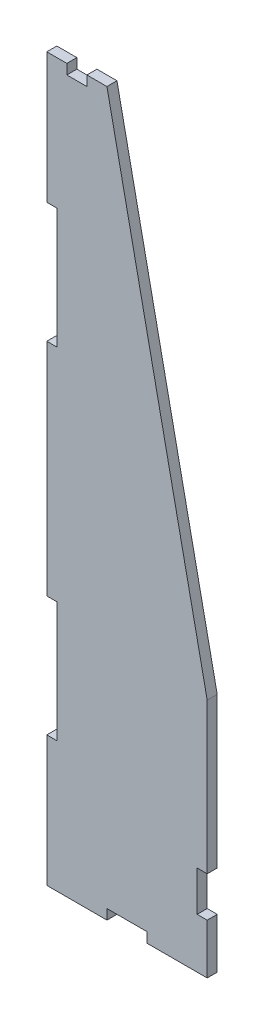
SolidWorks part; units mm, degrees
ref_plane "Front Plane" through (0, 0, 0) normal (0, 0, 1) x (1, 0, 0)
ref_plane "Top Plane" through (0, 0, 0) normal (0, 1, 0) x (1, 0, 0)
ref_plane "Right Plane" through (0, 0, 0) normal (1, 0, 0) x (0, 0, -1)
sketch "Sketch1" plane through (0, 0, 0) normal (0, 0, 1) x (1, 0, 0)
  line L0 (359.3199, 642.8699) -> (422.8199, 338.0699)
  line L1 (321.2199, 642.8699) -> (359.3199, 642.8699)
  line L2 (321.2199, 642.8699) -> (321.2199, 185.6699)
  line L3 (321.2199, 185.6699) -> (422.8199, 185.6699)
  line L4 (422.8199, 338.0699) -> (422.8199, 185.6699)
  dimension "D1" = 101.6
  dimension "D2" = 457.2
  dimension "D3" = 38.1
extrude "Boss-Extrude3" add sketch "Sketch1" along normal blind 6.35
sketch "Sketch2" plane through (0, 0, 6.35) normal (0, 0, 1) x (1, 0, 0)
  line L0 (327.5699, 642.8699) -> (327.5699, 185.6699) construction
  line L1 (359.3199, 642.8699) -> (321.2199, 642.8699) construction
  line L2 (321.2199, 185.6699) -> (422.8199, 185.6699) construction
  line L3 (321.2199, 192.0199) -> (422.8199, 192.0199) construction
  line L4 (321.2199, 642.8699) -> (321.2199, 185.6699) construction
  line L5 (422.8199, 185.6699) -> (422.8199, 338.0699) construction
  line L6 (321.2199, 636.5199) -> (360.6428, 636.5199) construction
  line L7 (416.4699, 185.6699) -> (416.4699, 368.5499) construction
  line L8 (422.8199, 338.0699) -> (359.3199, 642.8699) construction
  line L10 (346.6199, 642.8699) -> (333.9199, 642.8699)
  line L11 (346.6199, 642.8699) -> (346.6199, 636.5199)
  line L12 (346.6199, 636.5199) -> (333.9199, 636.5199)
  line L13 (333.9199, 642.8699) -> (333.9199, 636.5199)
  line L14 (321.2199, 560.3199) -> (327.5699, 560.3199)
  line L15 (321.2199, 560.3199) -> (321.2199, 484.1199)
  line L16 (321.2199, 484.1199) -> (327.5699, 484.1199)
  line L17 (327.5699, 560.3199) -> (327.5699, 484.1199)
  line L18 (321.2199, 344.4199) -> (327.5699, 344.4199)
  line L19 (321.2199, 344.4199) -> (321.2199, 268.2199)
  line L20 (321.2199, 268.2199) -> (327.5699, 268.2199)
  line L21 (327.5699, 344.4199) -> (327.5699, 268.2199)
  line L22 (359.3199, 192.0199) -> (384.7199, 192.0199)
  line L23 (359.3199, 192.0199) -> (359.3199, 185.6699)
  line L24 (359.3199, 185.6699) -> (384.7199, 185.6699)
  line L25 (384.7199, 192.0199) -> (384.7199, 185.6699)
  line L30 (416.4699, 242.8199) -> (422.8199, 242.8199)
  line L31 (416.4699, 242.8199) -> (416.4699, 217.4199)
  line L32 (416.4699, 217.4199) -> (422.8199, 217.4199)
  line L33 (422.8199, 242.8199) -> (422.8199, 217.4199)
  point P38 (419.6449, 217.4199)
  dimension "D1" = 6.35
  dimension "D2" = 6.35
  dimension "D3" = 6.35
  dimension "D4" = 6.35
  dimension "D6" = 12.7
  dimension "D8" = 82.55
  dimension "D9" = 82.55
  dimension "D10" = 25.4
  dimension "D14" = 31.75
  dimension "D7" = 25.4
  dimension "D13" = 38.1
  dimension "D5" = 12.7
  dimension "D11" = 76.2
extrude "Cut-Extrude1" cut sketch "Sketch2" against normal through all
equation "\"width\"= 3.5in"
equation "\"Height\"= 18in"
equation "\"D3@Sketch1\"=1.5"
equation "\"D4@Sketch1\"=\"Height\"/3"
equation "\"thick\"= 0.25"
equation "\"D1@Sketch2\"=\"thick\""
equation "\"D2@Sketch2\"=\"thick\""
equation "\"D3@Sketch2\"=\"thick\""
equation "\"D4@Sketch2\"=\"thick\""
equation "\"D2@Sketch1\"=\"Height\""
equation "\"D1@Sketch1\"=\"width\" + (\"thick\"*2)"
equation "\"D1@Boss-Extrude3\"=\"thick\""
